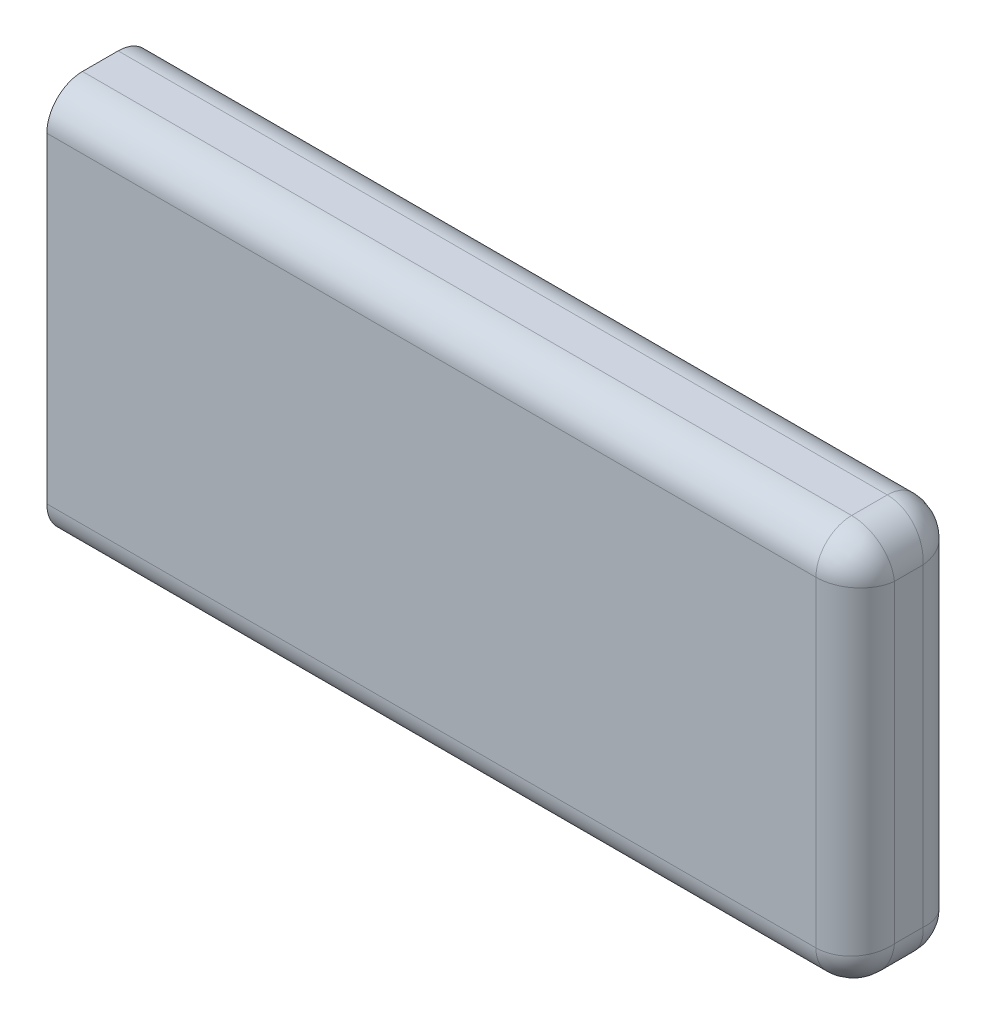
SolidWorks part; units mm, degrees
ref_plane "Front Plane" through (0, 0, 0) normal (0, 0, 1) x (1, 0, 0)
ref_plane "Top Plane" through (0, 0, 0) normal (0, 1, 0) x (1, 0, 0)
ref_plane "Right Plane" through (0, 0, 0) normal (1, 0, 0) x (0, 0, -1)
sketch "Sketch1" plane through (0, 0, 0) normal (0, 0, 1) x (1, 0, 0)
  line L1 (-84.0254, 42.2182) -> (88.6946, 42.2182)
  line L2 (-84.0254, 42.2182) -> (-84.0254, -41.6018)
  line L3 (-84.0254, -41.6018) -> (88.6946, -41.6018)
  line L4 (88.6946, 42.2182) -> (88.6946, -41.6018)
  dimension "D1" = 83.82
  dimension "D2" = 172.72
extrude "Boss-Extrude1" add sketch "Sketch1" along normal blind 22.86
fillet "Fillet1" radius 7.62 4 edges at (2.3346, 42.2182, 0) (2.3346, -41.6018, 0) (2.3346, -41.6018, 22.86) (2.3346, 42.2182, 22.86)
fillet "Fillet2" radius 8.382 8 edges at (88.6946, 0.3082, 0) (88.6946, -39.37, 2.2318) (88.6946, -41.6018, 11.43) (88.6946, -39.37, 20.6282) (88.6946, 0.3082, 22.86) (88.6946, 39.9863, 2.2318) (88.6946, 42.2182, 11.43) (88.6946, 39.9863, 20.6282)
